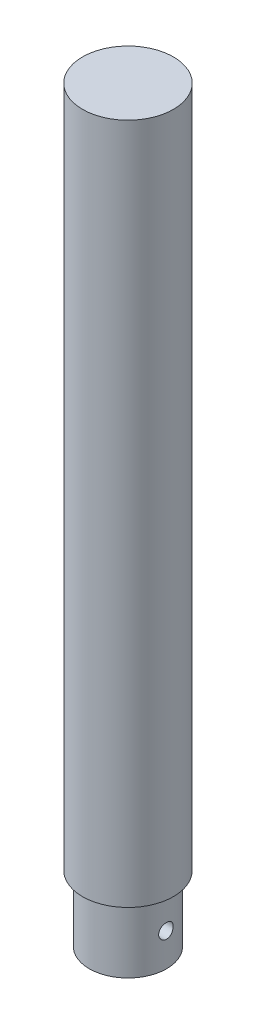
SolidWorks part; units mm, degrees
ref_plane "Front Plane" through (0, 0, 0) normal (0, 0, 1) x (1, 0, 0)
ref_plane "Top Plane" through (0, 0, 0) normal (0, 1, 0) x (1, 0, 0)
ref_plane "Right Plane" through (0, 0, 0) normal (1, 0, 0) x (0, 0, -1)
sketch "Sketch1" plane through (0, 0, 0) normal (0, 1, 0) x (1, 0, 0)
  line L0 (-10, 0) -> (10, 0)
  circle A0 centre (0, 0) radius 10
  point P7 (0, 0)
  dimension "D1" = 20
extrude "Boss-Extrude1" add sketch "Sketch1" along normal blind 150 contours A0
sketch "Sketch2" plane through (0, 0, 0) normal (0, -1, 0) x (1, 0, 0)
  circle A0 centre (0, 0) radius 8.5
  circle A1 centre (0, 0) radius 4.5
  dimension "D1" = 4
extrude "Boss-Extrude2" add sketch "Sketch2" along normal blind 14.5 contours A0 A1 region at (-8.2596, 0, 0)
sketch "Sketch3" plane through (0, 0, 0) normal (1, 0, 0) x (0, 0, -1)
  line L0 (0, 0) -> (0, -14.5) construction
  line L1 (-8.5, -14.5) -> (8.5, -14.5) construction
  circle A0 centre (0, -7.25) radius 1.6
extrude "Cut-Extrude1" cut sketch "Sketch3" against normal blind 14.5 and the other way blind 14.5
